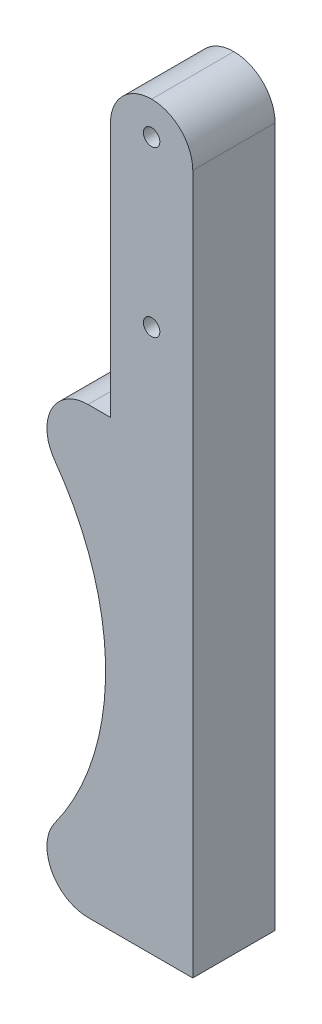
SolidWorks part; units mm, degrees
ref_plane "Front" through (0, 0, 0) normal (0, 0, 1) x (1, 0, 0)
ref_plane "Top" through (0, 0, 0) normal (0, 1, 0) x (1, 0, 0)
ref_plane "Right" through (0, 0, 0) normal (1, 0, 0) x (0, 0, -1)
sketch "Esquisse1" plane through (0, 0, 0) normal (0, 0, 1) x (1, 0, 0)
  line L1 (0, 0) -> (10, 0)
  line L2 (0, 0) -> (0, 90)
  line L3 (0, 90) -> (10, 90)
  line L4 (10, 0) -> (10, 90)
  dimension "D1" = 10
  dimension "D2" = 90
extrude "Boss.-Extru.1" add sketch "Esquisse1" along normal blind 10
sketch "Esquisse2" plane through (0, 0, 10) normal (0, 0, 1) x (1, 0, 0)
  line L0 (5, 90) -> (5, 66) construction
  line L1 (10, 90) -> (0, 90) construction
  circle A0 centre (5, 66) radius 1
  circle A1 centre (5, 86) radius 1
  dimension "D1" = 20
  dimension "D2" = 4
  dimension "D3" = 2
extrude "Enlèv. mat.-Extru.1" cut sketch "Esquisse2" against normal up to vertex (10 mm away) up to point (0, 90, 0)
fillet "Congé1" radius 5 2 edges at (10, 90, 5) (0, 90, 5)
sketch "Esquisse3" plane through (0, 0, 10) normal (0, 0, 1) x (1, 0, 0)
  line L0 (0, 0) -> (0, 54)
  line L1 (0, 85) -> (0, 0) construction
  line L2 (0, 54) -> (-15, 54)
  line L3 (-15, 0) -> (0, 0)
  line L4 (-15, 54) -> (-15, 0) construction
  line L5 (5, 0) -> (5, 34.4675) construction
  line L6 (0, 0) -> (10, 0) construction
  arc A0 (-15, 54) -> (-15, 0) centre (-33.0901, 27) cw
  dimension "D1" = 32.5
  dimension "D2" = 15
  dimension "D3" = 54
extrude "Boss.-Extru.2" add sketch "Esquisse3" against normal up to vertex (10 mm away) up to point (10, 0, 0)
fillet "Congé2" radius 5 2 edges at (-15, 54, 5) (-15, 0, 5)
